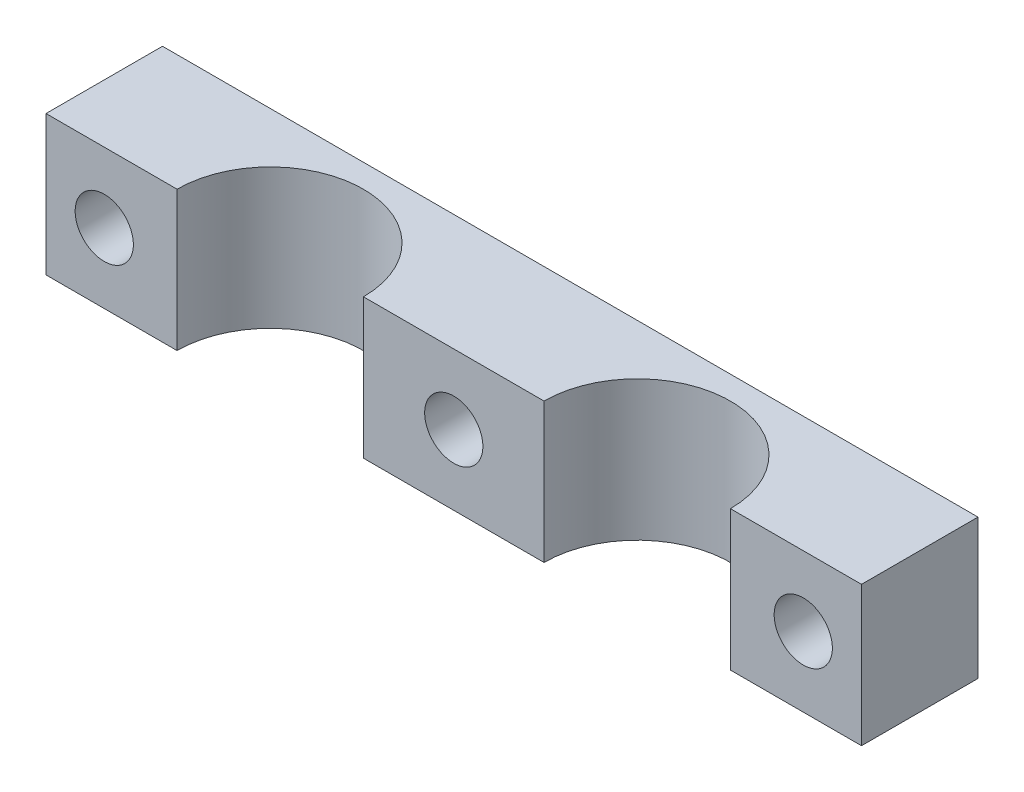
SolidWorks part; units mm, degrees
ref_plane "Front Plane" through (0, 0, 0) normal (0, 0, 1) x (1, 0, 0)
ref_plane "Top Plane" through (0, 0, 0) normal (0, 1, 0) x (1, 0, 0)
ref_plane "Right Plane" through (0, 0, 0) normal (1, 0, 0) x (0, 0, -1)
sketch "Sketch1" plane through (0, 0, 0) normal (0, 1, 0) x (1, 0, 0)
  line L1 (-35, 5) -> (35, 5)
  line L2 (-35, 5) -> (-35, -5)
  line L3 (-35, -5) -> (35, -5)
  line L4 (35, 5) -> (35, -5)
  line L5 (-35, 5) -> (35, -5) construction
  line L6 (-35, -5) -> (35, 5) construction
  circle A0 centre (0, 0) radius 2.5 construction
  circle A1 centre (-31.5, 0) radius 2.5 construction
  circle A2 centre (29.8554, 0) radius 2.5 construction
  circle A3 centre (-15.75, -5) radius 8
  circle A4 centre (15.75, -5) radius 8
  point P0 (0, 0)
  point P10 (-35, 0)
  point P15 (23.75, -5)
  dimension "D3" = 3.5
  dimension "D4" = 15.75
  dimension "D5" = 15.75
  dimension "D1" = 10
  dimension "D2" = 70
extrude "Boss-Extrude1" add sketch "Sketch1" along normal blind 12 contours A4 L3 L4 L1 L2 A3 region at (0, 0, -0.6467)
sketch "Sketch2" plane through (0, 0, -5) normal (0, 0, -1) x (-1, 0, 0)
  line L0 (-35, 12) -> (-35, 0) construction
  line L1 (35, 12) -> (35, 0) construction
  line L3 (35, 0) -> (-35, 0) construction
  circle A0 centre (0, 6) radius 2.5
  circle A1 centre (-30, 6) radius 2.5
  circle A2 centre (30, 6) radius 2.5
  point P6 (0, 0)
  dimension "D2" = 5
  dimension "D4" = 5
  dimension "D5" = 5
  dimension "D1" = 6
  dimension "D3" = 5
  dimension "D6" = 5
  dimension "D7" = 35
  dimension "D8" = 6
  dimension "D11" = 30
  dimension "D12" = 35
extrude "Cut-Extrude1" cut sketch "Sketch2" against normal up to surface (10 mm away) up to face at (29.375, 6, 5)
